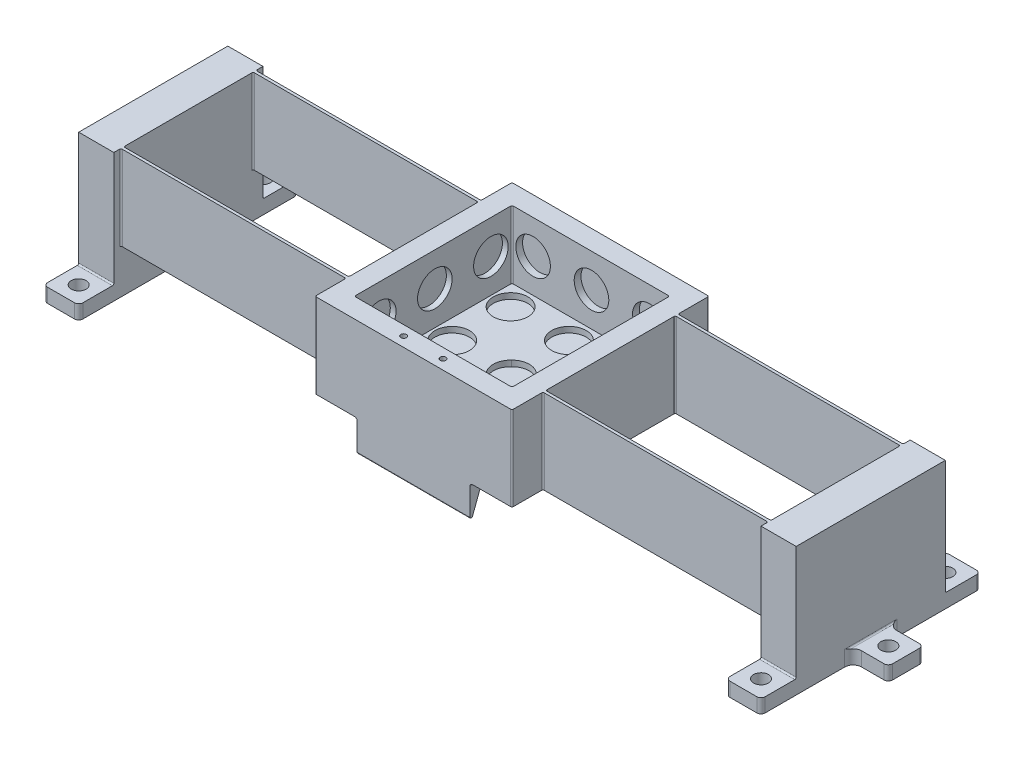
SolidWorks part; units mm, degrees
ref_plane "Front Plane" through (0, 0, 0) normal (0, 0, 1) x (1, 0, 0)
ref_plane "Top Plane" through (0, 0, 0) normal (0, 1, 0) x (1, 0, 0)
ref_plane "Right Plane" through (0, 0, 0) normal (1, 0, 0) x (0, 0, -1)
sketch "Sketch1" plane through (0, 0, 0) normal (0, 1, 0) x (1, 0, 0)
  line L1 (-35, -35) -> (35, -35)
  line L2 (-35, -35) -> (-35, 35)
  line L3 (-35, 35) -> (35, 35)
  line L4 (35, -35) -> (35, 35)
  line L5 (-35, -35) -> (35, 35) construction
  line L6 (-35, 35) -> (35, -35) construction
  point P0 (0, 0)
  dimension "D1" = 70
  dimension "D2" = 70
extrude "Boss-Extrude1" add sketch "Sketch1" along normal blind 30
shell "Shell1" thickness 7 removed face at (0, 30, 0)
sketch "Sketch2" plane through (0, 30, 0) normal (0, 1, 0) x (1, 0, 0)
  line L0 (-35, 35) -> (-35, -35) construction
  line L1 (-28, -28) -> (28, -28) construction
  line L2 (-28, -28) -> (-28, 28) construction
  line L3 (-28, 28) -> (28, 28) construction
  line L4 (28, -28) -> (28, 28) construction
  line L5 (-28, -28) -> (28, 28) construction
  line L6 (-28, 28) -> (28, -28) construction
  line L7 (35, 35) -> (-35, 35) construction
  point P0 (0, 0)
  dimension "D1" = 7
  dimension "D2" = 7
sketch "Sketch3" plane through (35, 0, 0) normal (1, 0, 0) x (0, 0, -1)
  line L0 (-35, 30) -> (35, 30) construction
  line L1 (-24, 30) -> (-23, 30)
  line L2 (-24, 30) -> (-24, 0)
  line L3 (-24, 0) -> (-23, 0)
  line L4 (-23, 30) -> (-23, 0)
  line L5 (-35, 0) -> (35, 0) construction
  line L11 (28, 30) -> (-28, 30) construction
  line L12 (24, 30) -> (23, 30)
  line L13 (24, 30) -> (24, 0)
  line L14 (24, 0) -> (23, 0)
  line L15 (23, 30) -> (23, 0)
  line L16 (-23.5, 30) -> (-23.5, 0) construction
  line L18 (23.5, 0) -> (23.5, 30) construction
  point P8 (0, 0)
  dimension "D1" = 1
  dimension "D2" = 23
  dimension "D3" = 23
extrude "Boss-Extrude2" add sketch "Sketch3" along normal blind 80
sketch "Sketch5" plane through (115, 0, 0) normal (1, 0, 0) x (0, 0, -1)
  line L0 (-24, 30) -> (-24, 0) construction
  line L1 (-26.5, 30) -> (26.5, 30)
  line L2 (-26.5, 30) -> (-26.5, 0)
  line L3 (-26.5, 0) -> (26.5, 0)
  line L4 (26.5, 30) -> (26.5, 0)
  line L5 (28, 30) -> (-28, 30) construction
  line L6 (24, 0) -> (35, 0) construction
  line L7 (24, 0) -> (24, 30) construction
  dimension "D1" = 2.5
  dimension "D2" = 2.5
extrude "Boss-Extrude3" add sketch "Sketch5" along normal blind 12.5
sketch "Sketch6" plane through (0, 0, 0) normal (0, -1, 0) x (1, 0, 0)
  line L1 (115, 26.5) -> (127.5, 26.5)
  line L2 (115, 26.5) -> (115, -26.5)
  line L3 (115, -26.5) -> (127.5, -26.5)
  line L4 (127.5, 26.5) -> (127.5, -26.5)
extrude "Boss-Extrude4" add sketch "Sketch6" along normal blind 15.75
sketch "Sketch8" plane through (0, -15.75, 0) normal (0, -1, 0) x (1, 0, 0)
  line L1 (127.5, -26.5) -> (115, -26.5)
  line L2 (127.5, -26.5) -> (127.5, -39)
  line L3 (127.5, -39) -> (115, -39)
  line L4 (115, -26.5) -> (115, -39)
  line L5 (127.5, 26.5) -> (115, 26.5)
  line L6 (127.5, 26.5) -> (127.5, 39)
  line L7 (127.5, 39) -> (115, 39)
  line L8 (115, 26.5) -> (115, 39)
  line L13 (127.5, -26.5) -> (127.5, 26.5) construction
  line L14 (140, -6.25) -> (127.5, -6.25)
  line L15 (140, -6.25) -> (140, 6.25)
  line L16 (140, 6.25) -> (127.5, 6.25)
  line L17 (127.5, -6.25) -> (127.5, 6.25)
  line L18 (140, -6.25) -> (127.5, 6.25) construction
  line L19 (140, 6.25) -> (127.5, -6.25) construction
  line L20 (127.5, 0) -> (140, 0) construction
  point P13 (133.75, 0)
  point P19 (127.5, 0)
  point P20 (127.5, 0)
extrude "Boss-Extrude5" add sketch "Sketch8" against normal blind 5
hole_wizard "Ø5.0mm Dowel Hole1" positions "Sketch9" profile "Sketch10" hole size "Ø5.0" standard "ANSI Metric"
sketch "Sketch9" plane through (0, -10.75, 0) normal (0, 1, 0) x (1, 0, 0)
  line L0 (121.25, 39) -> (121.25, 32.75) construction
  line L1 (115, 39) -> (127.5, 39) construction
  line L2 (121.25, 32.75) -> (127.5, 32.75) construction
  line L3 (127.5, 39) -> (127.5, 26.5) construction
  line L5 (127.5, 0) -> (133.75, 0) construction
  line L6 (127.5, -6.25) -> (127.5, 6.25) construction
  line L7 (133.75, 0) -> (133.75, 6.25) construction
  line L8 (127.5, 6.25) -> (140, 6.25) construction
  line L10 (121.25, -26.5) -> (121.25, -32.75) construction
  line L11 (115, -26.5) -> (127.5, -26.5) construction
  line L12 (121.25, -32.75) -> (127.5, -32.75) construction
  line L13 (127.5, -26.5) -> (127.5, -39) construction
  point P0 (121.25, 32.75)
  point P2 (133.75, 0)
  point P4 (121.25, -32.75)
sketch "Sketch10" plane through (121.25, -10.75, -32.75) normal (1, 0, 0) x (0, 0, 1)
  line L0 (0, 0) -> (0, 18.1023)
  line L1 (0, 18.1023) -> (2.65, 16.51)
  line L2 (2.65, 16.51) -> (2.65, 0)
  line L5 (2.65, 0) -> (0, 0)
  line L10 (0, 18.1023) -> (-2.65, 16.51) construction
  line L11 (0, -6.35) -> (0, 107.95) construction
  dimension "Hole Dia." = 5.3
  dimension "Hole Depth" = 16.51
  dimension "Drill Angle" = 118
mirror "Mirror1" about plane through (0, 0, 0) normal (1, 0, 0) of "Boss-Extrude2", "Boss-Extrude3", "Boss-Extrude5", "Boss-Extrude4", "Ø5.0mm Dowel Hole1"
fillet "Fillet1" radius 0.5 20 edges at (121.25, -10.75, 26.5) (-115, 15, 24) (-115, 15, 23) (-35, 15, 24) (-35, 15, 23) (-115, 15, -24) (-115, 15, -23) (-35, 15, -24) (-35, 15, -23) (-121.25, -10.75, -26.5) (-121.25, -10.75, 26.5) (35, 15, 24) (35, 15, 23) (115, 15, 24) (115, 15, 23) (35, 15, -24) (35, 15, -23) (115, 15, -24) (115, 15, -23) (121.25, -10.75, -26.5)
fillet "Fillet2" radius 1.5 12 edges at (140, -13.25, 6.25) (140, -13.25, -6.25) (127.5, -13.25, -39) (115, -13.25, -39) (127.5, -13.25, 39) (115, -13.25, 39) (-115, -13.25, -39) (-127.5, -13.25, -39) (-140, -13.25, -6.25) (-140, -13.25, 6.25) (-115, -13.25, 39) (-127.5, -13.25, 39)
sketch "Sketch11" plane through (0, 6, 0) normal (0, 1, 0) x (1, 0, 0)
  line L26 (-28, -28) -> (-28, 28) construction
  line L32 (-28, -28) -> (28, -28) construction
  circle A0 centre (-21, -21) radius 6.15
  dimension "D1" = 12.3
  dimension "D2" = 0.85
  dimension "D3" = 0.85
extrude "Cut-Extrude1" cut sketch "Sketch11" against normal blind 2.05
pattern_linear "LPattern1" count 3 spacing 20.75 along (1, 0, 0) count 3 spacing 20.75 along (0, 0, -1) of "Cut-Extrude1"
sketch "Sketch14" plane through (0, 6, 0) normal (0, 1, 0) x (1, 0, 0)
  line L0 (-28, 0) -> (0, 0) construction
  line L1 (-28, 28) -> (-28, -28) construction
  line L2 (0, 0) -> (0, -28) construction
  line L3 (-28, -28) -> (28, -28) construction
  circle A0 centre (0, 0) radius 6.15
  dimension "D1" = 12.3
extrude "Cut-Extrude4" cut sketch "Sketch14" against normal blind 2.05
sketch "Sketch12" plane through (-28, 0, 0) normal (1, 0, 0) x (0, 0, -1)
  line L5 (-28, 18) -> (-19.35, 18) construction
  line L6 (-28, 30) -> (-28, 6) construction
  circle A0 centre (-19.35, 18) radius 6.15
  dimension "D1" = 12.3
  dimension "D2" = 2.5
extrude "Cut-Extrude2" cut sketch "Sketch12" against normal blind 2.05
pattern_linear "LPattern2" count 3 spacing 19.925 along (0, 0, -1) of "Cut-Extrude2"
sketch "Sketch13" plane through (0, 0, -28) normal (0, 0, -1) x (-1, 0, 0)
  line L6 (-28, 30) -> (-28, 6) construction
  line L7 (-21, 18) -> (-28, 18) construction
  circle A0 centre (-21, 18) radius 6.15
  dimension "D1" = 12.3
  dimension "D3" = 0.85
extrude "Cut-Extrude3" cut sketch "Sketch13" along normal blind 2.4
pattern_linear "LPattern3" count 3 spacing 20.75 along (-1, 0, 0) of "Cut-Extrude3"
mirror "Mirror2" about plane through (0, 0, 0) normal (1, 0, 0) of "LPattern2", "Cut-Extrude2"
fillet "Fillet3" radius 0.5 4 edges at (28, 18, -28) (-28, 18, -28) (28, 18, 28) (-28, 18, 28)
fillet "Fillet4" radius 0.5 4 edges at (-35, 15, 35) (35, 15, 35) (-35, 15, -35) (35, 15, -35)
sketch "Sketch19" plane through (0, 0, 0) normal (1, 0, 0) x (0, 0, -1)
  line L0 (-30, 0) -> (-35, -13.25)
  line L1 (-35, -13.25) -> (-35, 0)
  line L2 (-35, 0) -> (-30, 0)
  line L3 (0, 0) -> (-30, 0) construction
  line L4 (37.5, -15.75) -> (-37.5, -15.75) construction
  dimension "D1" = 5
  dimension "D2" = 30
  dimension "D3" = 2.5
extrude "Boss-Extrude8" add sketch "Sketch19" along normal mid plane 40
sketch "Sketch20" plane through (0, 0, 0) normal (1, 0, 0) x (0, 0, -1)
  line L0 (-35, 20) -> (-42.5, 20)
  line L1 (-42.5, 20) -> (-42.5, 30)
  line L2 (-26.5, 30) -> (-42.5, 30) construction
  line L5 (-42.5, 30) -> (-40, 30)
  line L6 (-40, 30) -> (-40, 22.5)
  line L7 (-40, 22.5) -> (-35, 22.5)
  line L8 (-35, 22.5) -> (-35, 20)
  line L9 (-35, 30) -> (-35, 0) construction
  line L10 (-35, 0) -> (-35, 30) construction
  dimension "D1" = 5
  dimension "D2" = 10
  dimension "D3" = 2.5
  dimension "D4" = 2.5
extrude "Place For Sensor" [suppressed] add sketch "Sketch20" along normal mid plane 10
fillet "Place For Sensor Fillet5" [suppressed] radius 0.5
fillet "Place For Sensor Fillet6" [suppressed] radius 1.5
hole_wizard "Place For Sensor Ø3.0mm Dowel Hole2" [suppressed] positions "Sketch21" profile "Sketch22" hole size "Ø3.0" standard "ANSI Metric"
sketch "Sketch21" [suppressed] plane through (0, 0, 32.5) normal (0, 0, 1) x (1, 0, 0)
  line L0 (-2.5, 27.5) -> (2.5, 27.5) construction
  line L2 (-18, 30) -> (18, 30) construction
  line L3 (-5, 28.5) -> (-5, 20.5) construction
  line L4 (5, 28.5) -> (5, 20.5) construction
  point P0 (-2.5, 27.5)
  point P2 (2.5, 27.5)
  dimension "D1" = 2.5
  dimension "D2" = 2.5
  dimension "D3" = 2.5
sketch "Sketch22" plane through (-2.5, 27.5, 32.5) normal (1, 0, 0) x (0, -1, 0)
  line L0 (0, 0) -> (0, 2.5)
  line L1 (0, 2.5) -> (1.65, 2.5)
  line L2 (1.65, 2.5) -> (1.65, 0)
  line L5 (1.65, 0) -> (0, 0)
  line L11 (0, -6.35) -> (0, 107.95) construction
  dimension "Thru Hole Dia." = 3.3
  dimension "Thru Hole Depth" = 2.5
sketch "Sketch23" plane through (0, 30, 0) normal (0, 1, 0) x (1, 0, 0)
  line L1 (-28, -28) -> (28, -28) construction
  circle A0 centre (-7, -31.5) radius 1
  circle A1 centre (7, -31.5) radius 1
  dimension "D4" = 2
  dimension "D1" = 3.5
  dimension "D2" = 14
  dimension "D3" = 7
extrude "Cut-Extrude5" cut sketch "Sketch23" against normal blind 6
fillet "Fillet5" radius 0.5 1 edges at (0, -13.25, 35)
fillet "Fillet6" radius 1 3 edges at (-20, 0, 32.5) (20, 0, 32.5) (0, 0, 30)
fillet "Fillet8" radius 3 4 edges at (127.5, -13, 6.25) (127.5, -13, -6.25) (-127.5, -13, -6.25) (-127.5, -13, 6.25)
